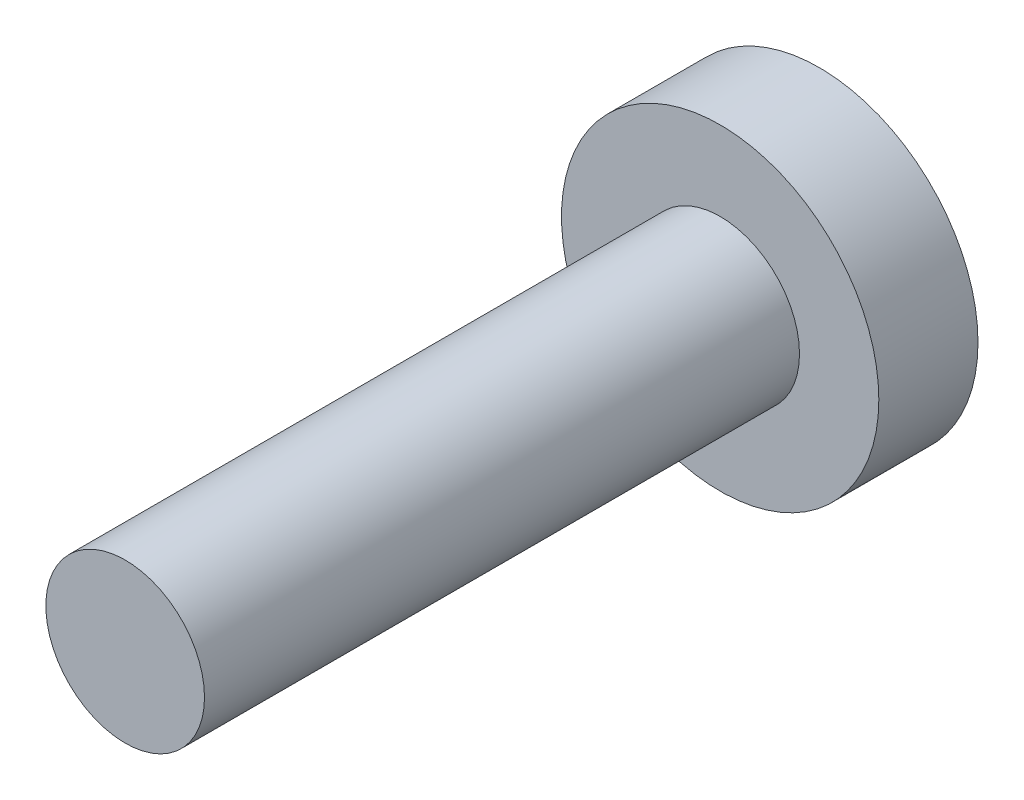
SolidWorks part; units mm, degrees
ref_plane "前视基准面" through (0, 0, 0) normal (0, 0, 1) x (1, 0, 0)
ref_plane "上视基准面" through (0, 0, 0) normal (0, 1, 0) x (1, 0, 0)
ref_plane "右视基准面" through (0, 0, 0) normal (1, 0, 0) x (0, 0, -1)
other "Configuration Table"
sketch "Sketch1" plane through (0, 0, 0) normal (0, 0, 1) x (1, 0, 0)
  circle A0 centre (0, 0) radius 8
extrude "Boss-Extrude1" add sketch "Sketch1" along normal blind 5
ref_plane "Plane1" through (0, 0, 5) normal (0, 0, 1) x (1, 0, 0)
sketch "Sketch2" plane through (0, 0, 5) normal (0, 0, 1) x (1, 0, 0)
  circle A0 centre (0, 0) radius 4
extrude "Boss-Extrude2" add sketch "Sketch2" along normal blind 30
sketch3d "3DSketch1"
  line L0 (0, 0, 0) -> (0, 0, 35) construction
ref_axis "screw_axis" through (0, 0, 0) along (0, 0, 1)
ref_plane "head_bottom_face" through (0, 0, 0) normal (0, 0, 1) x (1, 0, 0)
ref_plane "shank_end_face" through (0, 0, 35) normal (0, 0, 1) x (1, 0, 0)
